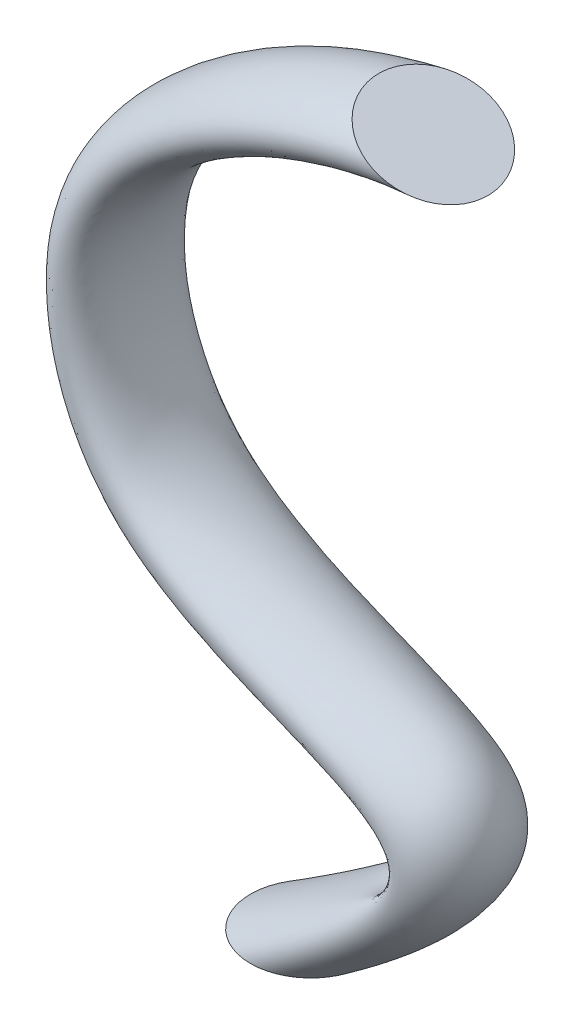
SolidWorks part; units mm, degrees
ref_plane "前视基准面" through (0, 0, 0) normal (0, 0, 1) x (1, 0, 0)
ref_plane "上视基准面" through (0, 0, 0) normal (0, 1, 0) x (1, 0, 0)
ref_plane "右视基准面" through (0, 0, 0) normal (1, 0, 0) x (0, 0, -1)
sketch "草图1" plane through (0, 0, 0) normal (0, 0, 1) x (1, 0, 0)
  spline S0 degree 3 poles (0, 0) (32.9017, 21.8792) (-13.5326, 17.5872) (-24.1177, 60.5547) (-0.1725, 72.7259) (12.1888, 74.559) knots 0 0 0 0 0.464188 0.6581 1 1 1 1
sketch "草图2" plane through (0, 0, 0) normal (0, 1, 0) x (1, 0, 0)
  circle A0 centre (0, 0) radius 6
sweep "扫描1" add profiles "草图2" path "草图1"
